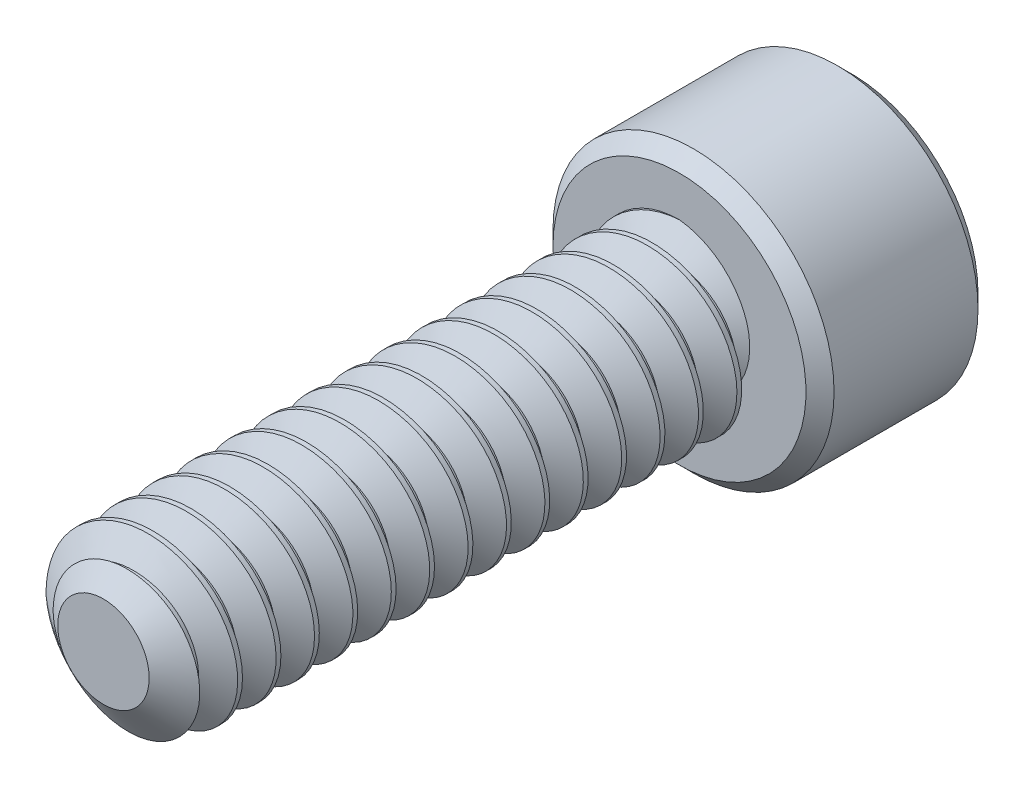
SolidWorks part; units mm, degrees
material "Alloy Steel"
ref_plane "Front Plane" through (0, 0, 0) normal (0, 0, 1) x (1, 0, 0)
ref_plane "Top Plane" through (0, 0, 0) normal (0, 1, 0) x (1, 0, 0)
ref_plane "Right Plane" through (0, 0, 0) normal (1, 0, 0) x (0, 0, -1)
sketch "Sketch1" plane through (0, 0, 0) normal (0, 0, 1) x (1, 0, 0)
  circle A0 centre (0, 0) radius 1.4224
  dimension "OD" = 2.8448
extrude "Extrude1" add sketch "Sketch1" against normal blind 9.525
sketch "Sketch2" plane through (0, 0, 0) normal (0, 0, 1) x (1, 0, 0)
  circle A0 centre (0, 0) radius 1.4224 construction
  circle A1 centre (0, 0) radius 1.4224
curve "Helix/Spiral1" pitch 0.635 height 10.16 turns 16 parameters "pitch"=0.635
sketch "Sketch3" plane through (0, 0, 0) normal (1, 0, 0) x (0, 0, -1)
  line L0 (-0.5556, 1.4224) -> (-0.3175, 1.01)
  line L1 (-0.3175, 1.01) -> (-0.2381, 1.01)
  line L2 (-0.2381, 1.01) -> (0, 1.4224)
  line L3 (-0.5556, 1.4224) -> (0, 1.4224)
  line L4 (-0.2778, 1.4224) -> (-0.2778, 1.01) construction
  line L5 (-0.4366, 1.2162) -> (-0.1191, 1.2162) construction
  line L6 (0, 1.4224) -> (0, -1.4224) construction
  dimension "D1" = 0.0794
  dimension "D2" = 0.3175
  dimension "D3" = 60
sweep "Cut-Sweep1" cut profiles "Sketch3" path "Helix/Spiral1"
sketch "Sketch4" plane through (0, 0, 0) normal (1, 0, 0) x (0, 0, -1)
  line L0 (0.4666, 1.4224) -> (0, 0.756)
  line L1 (0, 0.756) -> (0, 1.4224)
  line L2 (0.4666, 1.4224) -> (0, 1.4224)
  line L3 (-0.5556, 1.4224) -> (0, 1.4224) construction
  line L4 (0, 0) -> (7.0209, 0) construction
  dimension "D1" = 55
  dimension "D2" = 0.254
revolve "Cut-Revolve1" cut sketch "Sketch4" angle 360 about L4
sketch "Sketch5" plane through (0, 0, 0) normal (1, 0, 0) x (0, 0, -1)
  line L0 (9.525, -1.0232) -> (9.525, 1.0149) construction
  line L1 (9.525, 1.5494) -> (38.1885, 1.5494)
  line L2 (9.525, 1.5494) -> (9.525, 0)
  line L3 (9.525, 0) -> (38.1, 0)
  line L4 (38.1, 1.2192) -> (38.1, 0)
  line L5 (38.1885, 1.5494) -> (38.1, 1.2192)
  line L6 (0, 0) -> (9.9695, 0) construction
  point P3 (38.1, 1.5494)
  point P10 (38.1, 1.5494)
  dimension "D1" = 0.3302
  dimension "Thread min" = 38.1
  dimension "D2" = 0.127
  dimension "D3" = 15
revolve "partially thread" [suppressed] add sketch "Sketch5" angle 360 about L6
sketch "Sketch6" plane through (0, 0, -9.525) normal (0, 0, -1) x (-1, 0, 0)
  circle A0 centre (0, 0) radius 2.3241
  dimension "head dia" = 4.6482
extrude "Extrude2" add sketch "Sketch6" along normal blind 2.8448
sketch "Sketch7" plane through (0, 0, -12.3698) normal (0, 0, -1) x (-1, 0, 0)
  line L1 (0, 1.3748) -> (-1.1906, 0.6874)
  line L2 (-1.1906, 0.6874) -> (-1.1906, -0.6874)
  line L3 (-1.1906, -0.6874) -> (0, -1.3748)
  line L4 (0, -1.3748) -> (1.1906, -0.6874)
  line L5 (1.1906, -0.6874) -> (1.1906, 0.6874)
  line L6 (1.1906, 0.6874) -> (0, 1.3748)
  circle A0 centre (0, 0) radius 1.1906 construction
  dimension "hex dia" = 2.3813
extrude "Cut-Extrude1" cut sketch "Sketch7" against normal blind 1.7859
sketch "Sketch8" plane through (0, 0, -12.3698) normal (0, 0, -1) x (-1, 0, 0)
  circle A0 centre (0, 0) radius 1.3748
extrude "Cut-Extrude2" cut sketch "Sketch8" against normal through all draft 45
chamfer "Chamfer1" distance 0.2324 angle 45 2 edges at (-2.3241, 0, -12.3698) (-2.3241, 0, -9.525)
sketch "Sketch9" plane through (0, 0, 0) normal (1, 0, 0) x (0, 0, -1)
  line L0 (0, 1.4224) -> (0, -1.4224) construction
  line L1 (6.6675, 1.4224) -> (6.6675, -1.4224) construction
  dimension "D1" = 6.6675
equation "\"D3@Helix/Spiral1\" = \"screw length@Extrude1\"+\"pitch@Helix/Spiral1\""
equation "\"D1@Sketch3\" = \"pitch@Helix/Spiral1\"*.125"
equation "\"D2@Sketch3\" = \"pitch@Helix/Spiral1\"*.5"
equation "\"D1@Cut-Extrude1\" = \"hex dia@Sketch7\"*.75"
equation "\"D1@Chamfer1\" = \"head dia@Sketch6\"*.05"
equation "\"D1@Sketch9\" = \"pitch@Helix/Spiral1\"*10.5"
